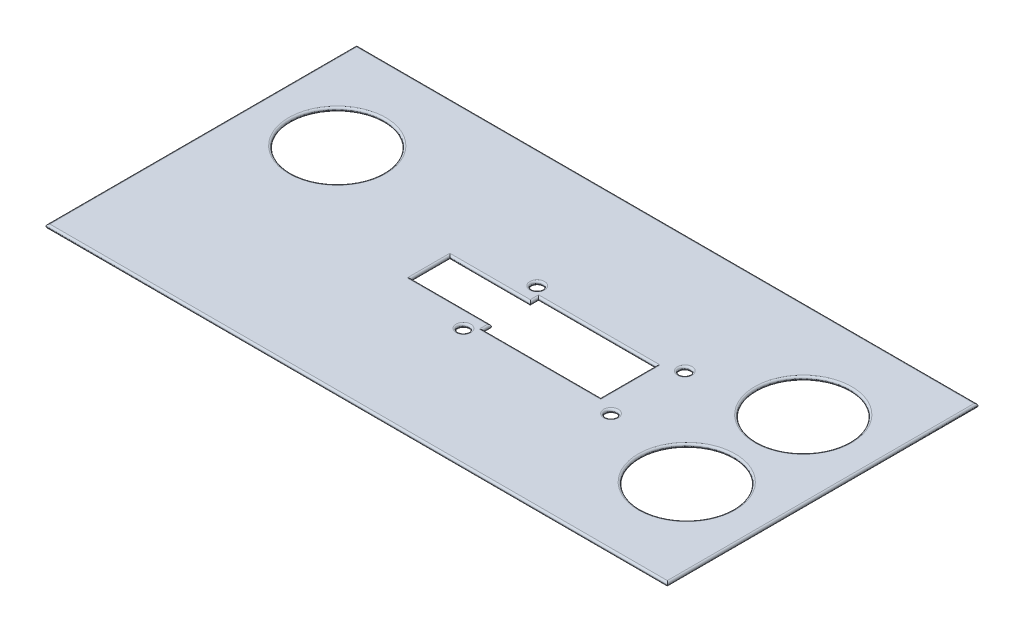
SolidWorks part; units mm, degrees
ref_plane "Front Plane" through (0, 0, 0) normal (0, 0, 1) x (1, 0, 0)
ref_plane "Top Plane" through (0, 0, 0) normal (0, 1, 0) x (1, 0, 0)
ref_plane "Right Plane" through (0, 0, 0) normal (1, 0, 0) x (0, 0, -1)
sketch "Sketch1" plane through (0, 0, 0) normal (0, 1, 0) x (1, 0, 0)
  line L0 (-96, 15) -> (64, 15) construction
  line L1 (44, 15) -> (44, -15) construction
  line L2 (-19, 9.5) -> (19, 9.5) construction
  line L3 (-19, 9.5) -> (-19, -9.5) construction
  line L4 (-19, -9.5) -> (19, -9.5) construction
  line L5 (19, 9.5) -> (19, -9.5) construction
  line L6 (0, -9.5) -> (0, 9.5) construction
  line L7 (-19, 0) -> (19, 0) construction
  line L8 (-37, 5) -> (-16.3, 5)
  line L9 (-37, 5) -> (-37, -5)
  line L10 (-37, -5) -> (-16.3, -5)
  line L12 (-26.65, -5) -> (-26.65, 5) construction
  line L13 (-37, 0) -> (-19, 0) construction
  line L14 (44, 0) -> (-96, 0) construction
  line L15 (-96, 15) -> (-96, -40)
  line L16 (-96, -40) -> (64, -40)
  line L17 (64, -40) -> (64, 15)
  line L18 (64, 15) -> (64, 40)
  line L19 (64, 40) -> (-96, 40)
  line L20 (-96, 40) -> (-96, 15)
  line L21 (44, 15) -> (44, 40) construction
  line L22 (44, -15) -> (44, -40) construction
  line L23 (-1.15, 7.15) -> (-1.15, 9.5) construction
  line L24 (-1.15, -7.15) -> (-1.15, -9.5) construction
  line L25 (-16.3, 7.15) -> (14, 7.15)
  line L27 (-16.3, -7.15) -> (14, -7.15)
  line L28 (14, 7.15) -> (14, -7.15)
  line L29 (-16.3, -7.15) -> (-16.3, -5)
  line L30 (-16.3, 5) -> (-16.3, 7.15)
  circle A0 centre (44, 15) radius 12
  circle A1 centre (-76, 15) radius 12
  circle A2 centre (19, -9.5) radius 1.4
  circle A3 centre (-19, -9.5) radius 1.4
  circle A4 centre (-19, 9.5) radius 1.4
  circle A5 centre (19, 9.5) radius 1.4
  circle A6 centre (44, -15) radius 12
  point P8 (-26.65, 0)
  point P11 (0, 0)
  dimension "D1" = 24
  dimension "D9" = 2.8
  dimension "D2" = 20
  dimension "D3" = 20
  dimension "D4" = 38
  dimension "D5" = 19
  dimension "D6" = 18
  dimension "D7" = 10
  dimension "D8" = 30.3
  dimension "D10" = 30
  dimension "D11" = 25
  dimension "D12" = 160
  dimension "D13" = 80
  dimension "D14" = 14.3
  dimension "D15" = 5
extrude "Boss-Extrude1" add sketch "Sketch1" along normal blind 1
fillet "Fillet1" radius 0.5 38 edges at (19, 0, -8.1) (-19, 0, -8.1) (19, 0, 10.9) (-19, 0, 10.9) (-26.65, 0, 5) (-37, 0, 0) (-26.65, 0, -5) (-16, 0, 40) (64, 0, 0) (-16, 0, -40) (-96, 0, 0) (44, 0, -3) (-76, 0, -3) (44, 0, 27) (19, 1, -8.1) (19, 1, 10.9) (-37, 1, 0) (-26.65, 1, 5) (-26.65, 1, -5) (44, 1, 27) (44, 1, -3) (-16, 1, -40) (64, 1, 0) (-16, 1, 40) (-96, 1, 0) (-76, 1, -3) (-19, 1, 10.9) (-19, 1, -8.1) (-1.15, 0, -7.15) (14, 0, 0) (-1.15, 0, 7.15) (14, 1, 0) (-1.15, 1, -7.15) (-1.15, 1, 7.15) (-16.3, 0, -6.075) (-16.3, 0, 6.075) (-16.3, 1, -6.075) (-16.3, 1, 6.075)
